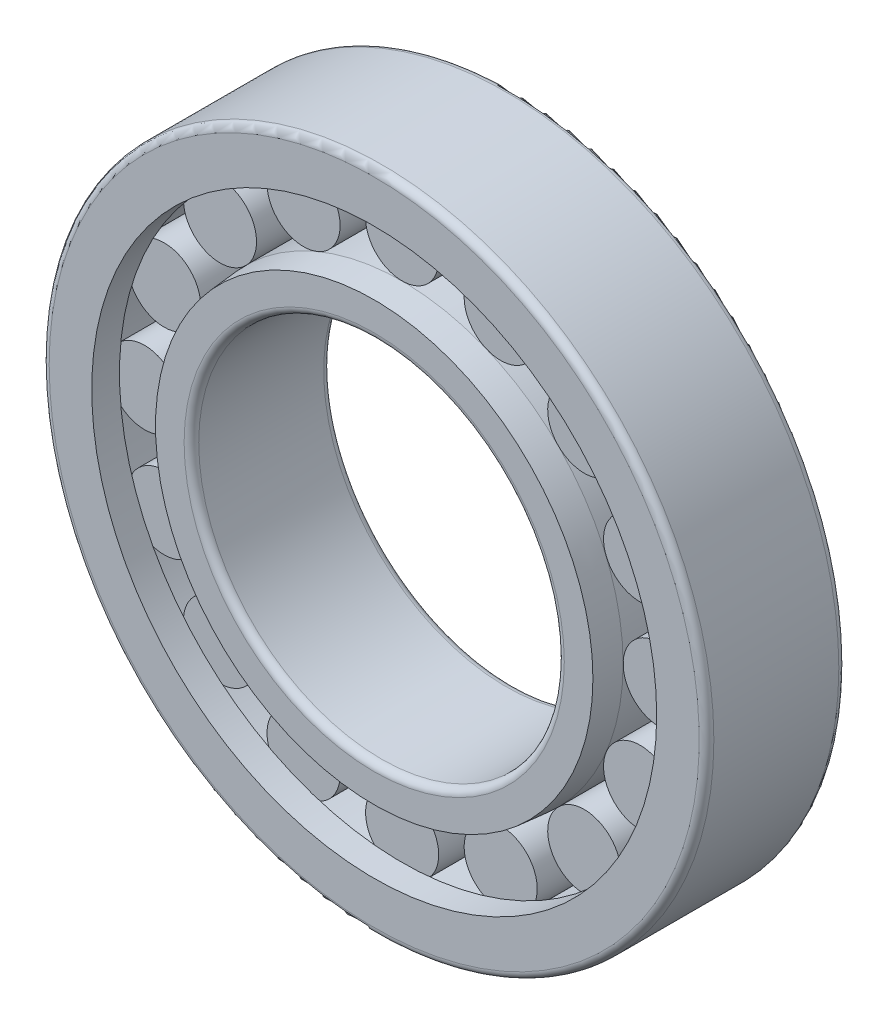
SolidWorks part; units mm, degrees
ref_plane "Front Plane" through (0, 0, 0) normal (0, 0, 1) x (1, 0, 0)
ref_plane "Top Plane" through (0, 0, 0) normal (0, 1, 0) x (1, 0, 0)
ref_plane "Right Plane" through (0, 0, 0) normal (1, 0, 0) x (0, 0, -1)
sketch "BaseSke" plane through (0, 0, 0) normal (1, 0, 0) x (0, 0, -1)
  line L0 (-47.2296, 0) -> (24.6132, 0) construction
  line L1 (-47.2296, 38.75) -> (24.6132, 38.75) construction
  line L2 (0, 129.5214) -> (0, -86.3012) construction
  line L3 (-6.3, 38.75) -> (-6.3, 44.25) construction
  line L4 (-10.5, 50) -> (10.5, 50) construction
  line L5 (-10.5, 27.5) -> (10.5, 27.5) construction
  line L6 (-6.3, 33.25) -> (6.3, 33.25)
  line L7 (-6.3, 33.25) -> (-6.3, 38.75)
  line L8 (-6.3, 38.75) -> (6.3, 38.75)
  line L9 (6.3, 33.25) -> (6.3, 38.75)
  line L10 (-6.3, 44.25) -> (6.3, 44.25) construction
  line L11 (6.3, 44.25) -> (6.3, 38.75) construction
  dimension "D2" = 12.6
revolve "Roller" add sketch "BaseSke" angle 360 about L8
sketch "OuterRaceSke" plane through (0, 0, 0) normal (1, 0, 0) x (0, 0, -1)
  line L0 (0, 0) -> (0, 87.5396) construction
  line L1 (-10.5, 50) -> (10.5, 50)
  line L2 (-10.5, 50) -> (-10.5, 42.5)
  line L3 (-10.5, 42.5) -> (-6.325, 42.5)
  line L4 (10.5, 50) -> (10.5, 42.5)
  line L5 (-50.3916, 0) -> (55.2197, 0) construction
  line L6 (-6.3, 44.25) -> (6.3, 44.25) construction
  line L7 (6.325, 42.5) -> (10.5, 42.5)
  line L9 (-6.325, 42.5) -> (-6.325, 44.23)
  line L10 (-6.325, 44.23) -> (6.325, 44.23)
  line L11 (6.325, 42.5) -> (6.325, 44.23)
  dimension "D2" = 85
  dimension "D1" = 12.65
  dimension "D3" = 0.02
revolve "OuterRace" add sketch "OuterRaceSke" angle 360 about L5
sketch "InnerRaceSke" plane through (0, 0, 0) normal (1, 0, 0) x (0, 0, -1)
  line L0 (-70.8626, 0) -> (113.5527, 0) construction
  line L1 (0, 58.441) -> (0, -70.8113) construction
  line L2 (-10.5, 27.5) -> (10.5, 27.5)
  line L3 (-10.5, 27.5) -> (-10.5, 35)
  line L4 (-6.325, 35) -> (-6.325, 33.27)
  line L5 (-6.325, 35) -> (-10.5, 35)
  line L6 (0, 129.5214) -> (0, -86.3012) construction
  line L7 (-6.325, 33.27) -> (6.325, 33.27)
  line L9 (10.5, 27.5) -> (10.5, 35)
  line L10 (6.325, 35) -> (10.5, 35)
  line L11 (6.325, 33.27) -> (6.325, 35)
  line L13 (-6.3, 33.25) -> (6.3, 33.25) construction
  point P17 (0, 27.5)
  dimension "D1" = 12.65
  dimension "D2" = 0.02
  dimension "D3" = 70
revolve "InnerRace" add sketch "InnerRaceSke" angle 360 about L0
fillet "Fillet1" radius 1.1 4 edges at (27.5, 0, 10.5) (50, 0, -10.5) (50, 0, 10.5) (27.5, 0, -10.5)
sketch "CutGrooveSke" plane through (0, 0, 0) normal (1, 0, 0) x (0, 0, -1)
  line L0 (-51.8407, 0) -> (83.8302, 0) construction
  line L1 (-5.25, -69) -> (-6.3, -69)
  line L2 (-5.25, -69) -> (-5.25, -49)
  line L3 (-5.25, -49) -> (-6.3, -49)
  line L4 (-6.3, -69) -> (-6.3, -49)
  dimension "D1" = 49
  dimension "D3" = 1.05
  dimension "D4" = 20
  dimension "D2" = 5.25
revolve "CutGroove" [suppressed] cut sketch "CutGrooveSke" angle 360 about L0
sketch "TaperSke" plane through (0, 0, 0) normal (1, 0, 0) x (0, 0, -1)
  line L0 (-10.5, 27.5) -> (10.5, 27.5)
  line L1 (10.5, 27.5) -> (10.5, 29.25)
  line L2 (10.5, 29.25) -> (-10.5, 27.5)
  line L7 (-41.2502, 0) -> (40.8606, 0) construction
revolve "Taper" [suppressed] cut sketch "TaperSke" angle 360 about L7
fillet "Fillet2" [suppressed] radius 1.1
sketch "NFSke" plane through (0, 0, 0) normal (1, 0, 0) x (0, 0, -1)
  line L0 (-54.6114, 0) -> (63.7655, 0) construction
  line L1 (10.5, 44.5953) -> (6.325, 44.23)
  line L2 (6.325, 44.23) -> (6.325, 42.5)
  line L3 (6.325, 42.5) -> (10.5, 42.5)
  line L4 (10.5, 42.5) -> (10.5, 44.5953)
  dimension "D1" = 5
revolve "NF" [suppressed] cut sketch "NFSke" angle 360 about L0
mirror "N" [suppressed] about plane through (0, 0, 0) normal (0, 0, 1)
sketch "NJSke" plane through (0, 0, 0) normal (1, 0, 0) x (0, 0, -1)
  line L0 (-35.6078, 0) -> (44.429, 0) construction
  line L1 (10.5, 35) -> (6.325, 35)
  line L2 (6.325, 35) -> (6.325, 33.27)
  line L3 (6.325, 33.27) -> (10.5, 32.9047)
  line L4 (10.5, 32.9047) -> (10.5, 35)
  dimension "D1" = 5
revolve "NJ" cut sketch "NJSke" angle 360 about L0
mirror "NU" about plane through (0, 0, 0) normal (0, 0, 1) of "NJ"
pattern_circular "CirPatternBall" count 16 over 360 about axis through (0, 0, 50.3916) along (0, 0, -1) of "Roller"
sketch "SimplifiedSke" plane through (0, 0, 0) normal (1, 0, 0) x (0, 0, -1)
  line L0 (37.5911, 0) -> (-37.5911, 0) construction
  line L1 (-13.1351, 38.75) -> (13.151, 38.75) construction
  line L2 (-6.3, 44.25) -> (6.3, 44.25)
  line L3 (-6.3, 44.25) -> (-6.3, 33.25)
  line L4 (-6.3, 33.25) -> (6.3, 33.25)
  line L5 (6.3, 44.25) -> (6.3, 33.25)
  line L6 (-47.2296, 38.75) -> (24.6132, 38.75) construction
revolve "Simplified" [suppressed] add sketch "SimplifiedSke" angle 360 about L0
equation "\"D2@BaseSke\" = \"Bearing_Thickness@BaseSke\"*0.6"
equation "\"D1@OuterRaceSke\" = \"Bearing_Thickness@BaseSke\"*0.6+0.05"
equation "\"D2@OuterRaceSke\" =\"Bearing_Outside_Diameter@BaseSke\" -  ( \"Bearing_Outside_Diameter@BaseSke\" - \"Bearing_Inside_Diameter@BaseSke\"  )/ 3 "
equation "\"D1@InnerRaceSke\" = \"Bearing_Thickness@BaseSke\"*0.6+0.05"
equation "\"D3@InnerRaceSke\" = \"Bearing_Inside_Diameter@BaseSke\" +  ( \"Bearing_Outside_Diameter@BaseSke\" - \"Bearing_Inside_Diameter@BaseSke\" ) / 3 "
equation "\"D1@CirPatternBall\" =  int(  ( \"Bearing_Outside_Diameter@BaseSke\" + \"Bearing_Inside_Diameter@BaseSke\" )  / 2 *  pi  /  ( \"Bearing_Outside_Diameter@BaseSke\" - \"Bearing_Inside_Diameter@BaseSke\" ) * 3 ) "
equation "\"D1@CutGrooveSke\" = \"Bearing_Outside_Diameter@BaseSke\" * 0.49"
equation "\"D2@CutGrooveSke\" = \"Bearing_Thickness@BaseSke\" *0.25"
equation "\"D3@CutGrooveSke\" = \"Bearing_Thickness@BaseSke\"/20"
equation "\"Taper@TaperSke\" = \"Bearing_Thickness@BaseSke\"/12"
equation "\"D1@Fillet2\" = \"Fillet_radius@Fillet1\""
